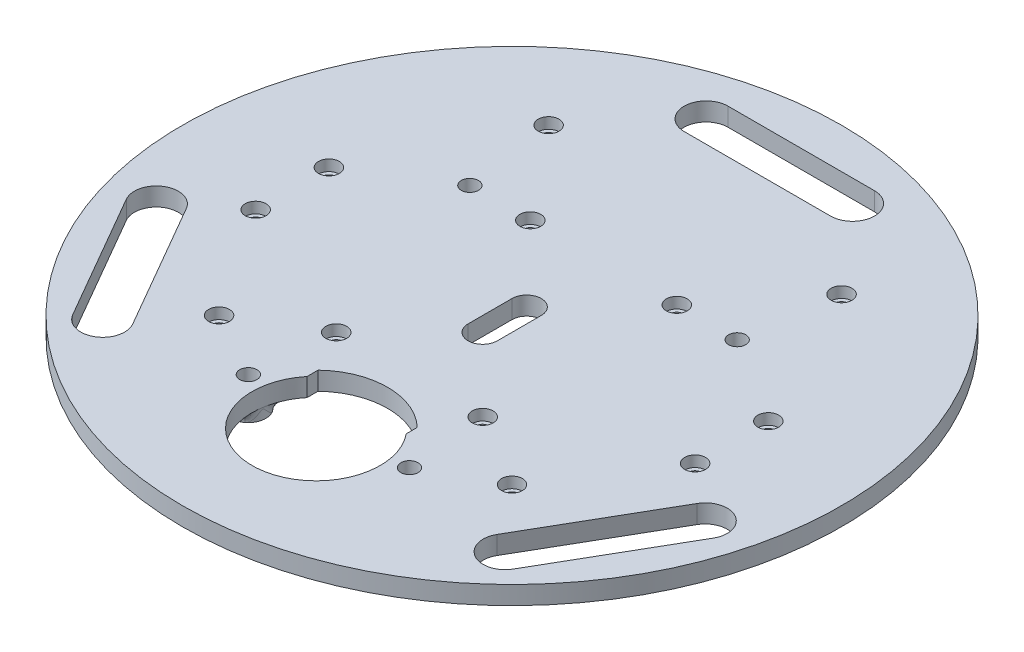
SolidWorks part; units mm, degrees
ref_plane "Front Plane" through (0, 0, 0) normal (0, 0, 1) x (1, 0, 0)
ref_plane "Top Plane" through (0, 0, 0) normal (0, 1, 0) x (1, 0, 0)
ref_plane "Right Plane" through (0, 0, 0) normal (1, 0, 0) x (0, 0, -1)
sketch "Sketch1" plane through (0, 0, 0) normal (0, 1, 0) x (1, 0, 0)
  line L0 (0, 0) -> (0, 77.033) construction
  circle A0 centre (-36.5, 25) radius 2.35
  circle A1 centre (-22, -50) radius 2.35
  circle A3 centre (22, -50) radius 2.35
  circle A4 centre (36.5, 25) radius 2.35
  circle A7 centre (0, 0) radius 90
  point P13 (0, 0)
  point P14 (0, 0)
  dimension "D2" = 4.7
  dimension "D7" = 180
  dimension "D1" = 36.5
  dimension "D4" = 22
  dimension "D5" = 50
  dimension "D6" = 25
extrude "Boss-Extrude1" add sketch "Sketch1" along normal blind 5
sketch "Sketch2" plane through (0, 5, 0) normal (0, 1, 0) x (1, 0, 0)
  circle A12 centre (0, -53.5) radius 17.5
  circle A14 centre (-22, -50) radius 2.35 construction
  point P3 (0, 0)
  dimension "D1" = 35
  dimension "D2" = 3.5
extrude "Cut-Extrude1" cut sketch "Sketch2" against normal up to next
sketch "Sketch3" plane through (0, 5, 0) normal (0, 1, 0) x (1, 0, 0)
  line L0 (0, 4) -> (0, -8) construction
  line L1 (4, 4) -> (4, -8)
  line L2 (-4, 4) -> (-4, -8)
  line L3 (0, -2) -> (0, 95.8356) construction
  line L4 (0, -2) -> (92.6321, -55.4812) construction
  line L5 (0, -2) -> (-96.3084, -57.6037) construction
  line L6 (-74.9519, -22.1795) -> (-54.9519, -56.8205) construction
  line L7 (-69.7558, -19.1795) -> (-49.7558, -53.8205)
  line L8 (-80.1481, -25.1795) -> (-60.1481, -59.8205)
  line L9 (-20, 73) -> (20, 73) construction
  line L10 (-20, 79) -> (20, 79)
  line L11 (-20, 67) -> (20, 67)
  line L12 (74.9519, -22.1795) -> (54.9519, -56.8205) construction
  line L13 (80.1481, -25.1795) -> (60.1481, -59.8205)
  line L14 (69.7558, -19.1795) -> (49.7558, -53.8205)
  arc A0 (4, 4) -> (-4, 4) centre (0, 4) ccw
  arc A1 (-4, -8) -> (4, -8) centre (0, -8) ccw
  arc A2 (-69.7558, -19.1795) -> (-80.1481, -25.1795) centre (-74.9519, -22.1795) ccw
  arc A3 (-60.1481, -59.8205) -> (-49.7558, -53.8205) centre (-54.9519, -56.8205) ccw
  arc A4 (-20, 79) -> (-20, 67) centre (-20, 73) ccw
  arc A5 (20, 67) -> (20, 79) centre (20, 73) ccw
  arc A6 (80.1481, -25.1795) -> (69.7558, -19.1795) centre (74.9519, -22.1795) ccw
  arc A7 (49.7558, -53.8205) -> (60.1481, -59.8205) centre (54.9519, -56.8205) ccw
  point P3 (0, -2)
  point P14 (-64.9519, -39.5)
  point P19 (0, 73)
  point P26 (64.9519, -39.5)
  point P33 (0, 78.7778)
  point P34 (62.957, -38.3482)
  dimension "D3" = 4
  dimension "D2" = 12
  dimension "D1" = 2
  dimension "D4" = 120
  dimension "D5" = 120
  dimension "D6" = 40
  dimension "D7" = 6
  dimension "D8" = 75
  dimension "D9" = 75
  dimension "D10" = 75
extrude "Cut-Extrude2" cut sketch "Sketch3" against normal up to next and the other way through all
sketch "Sketch4" plane through (0, 0, 0) normal (0, -1, 0) x (1, 0, 0)
  circle A0 centre (-36.5, -25) radius 4.75
  circle A1 centre (-22, 50) radius 4.75
  circle A2 centre (22, 50) radius 4.75
  circle A3 centre (36.5, -25) radius 4.75
  circle A4 centre (-22, 50) radius 2.35 construction
  circle A5 centre (36.5, -25) radius 2.35 construction
  circle A6 centre (-36.5, -25) radius 2.35 construction
  circle A7 centre (22, 50) radius 2.35 construction
  circle A8 centre (-22, 50) radius 2.35
  circle A9 centre (36.5, -25) radius 2.35
  circle A10 centre (-36.5, -25) radius 2.35
  circle A11 centre (22, 50) radius 2.35
  dimension "D1" = 9.5
extrude "Boss-Extrude3" add sketch "Sketch4" along normal blind 3
fillet "Fillet1" radius 3 4 edges at (-36.5, 0, -20.25) (36.5, 0, -20.25) (22, 0, 54.75) (-22, 0, 54.75)
sketch "Sketch5" plane through (0, 0, 0) normal (0, -1, 0) x (1, 0, 0)
  line L0 (-13.55, 42.4254) -> (-13.55, 39.4261)
  line L1 (13.5528, 42.4289) -> (13.5528, 39.4289)
  arc A0 (-13.55, 42.4254) -> (13.5528, 42.4289) centre (0, 53.5) ccw
  arc A1 (-15.6174, 45.604) -> (15.6174, 45.604) centre (0, 53.5) ccw construction
  arc A2 (-13.55, 39.4261) -> (13.5528, 39.4289) centre (0, 53.5) ccw
  dimension "D1" = 17.5
  dimension "D2" = 31
  dimension "D3" = 13.55
  dimension "D4" = 3
extrude "Cut-Extrude3" cut sketch "Sketch5" against normal up to next
sketch "Sketch6" plane through (0, 0, 0) normal (0, -1, 0) x (1, 0, 0)
  line L0 (0, 0) -> (0, 56.8674) construction
  circle A0 centre (-60, -10) radius 1.8
  circle A1 centre (-40, -50) radius 1.8
  circle A2 centre (-40, 40) radius 1.8
  circle A3 centre (-60, 10) radius 1.8
  circle A4 centre (-20, -25) radius 1.8
  circle A5 centre (-20, 28) radius 1.8
  circle A7 centre (20, 28) radius 1.8
  circle A8 centre (20, -25) radius 1.8
  circle A9 centre (60, 10) radius 1.8
  circle A10 centre (40, 40) radius 1.8
  circle A11 centre (40, -50) radius 1.8
  circle A12 centre (60, -10) radius 1.8
  dimension "D1" = 3.6
  dimension "D2" = 20
  dimension "D3" = 20
  dimension "D4" = 25
  dimension "D5" = 28
  dimension "D6" = 40
  dimension "D7" = 40
  dimension "D8" = 10
  dimension "D9" = 60
  dimension "D10" = 60
  dimension "D11" = 10
  dimension "D12" = 40
  dimension "D13" = 50
extrude "Cut-Extrude4" cut sketch "Sketch6" against normal up to next
sketch "Sketch7" plane through (0, 5, 0) normal (0, 1, 0) x (1, 0, 0)
  line L0 (0, 0) -> (0, 101.9726) construction
  circle A0 centre (-40, 50) radius 2.85
  circle A1 centre (-20, 25) radius 2.85
  circle A2 centre (-60, 10) radius 2.85
  circle A3 centre (-60, -10) radius 2.85
  circle A4 centre (-40, -40) radius 2.85
  circle A6 centre (-20, -28) radius 2.85
  circle A7 centre (20, -28) radius 2.85
  circle A8 centre (40, -40) radius 2.85
  circle A9 centre (60, -10) radius 2.85
  circle A10 centre (60, 10) radius 2.85
  circle A11 centre (20, 25) radius 2.85
  circle A12 centre (40, 50) radius 2.85
  dimension "D1" = 5.7
extrude "Cut-Extrude5" cut sketch "Sketch7" against normal blind 3
equation "\"D9@Sketch3\"=\"D8@Sketch3\""
equation "\"D10@Sketch3\"=\"D8@Sketch3\""
